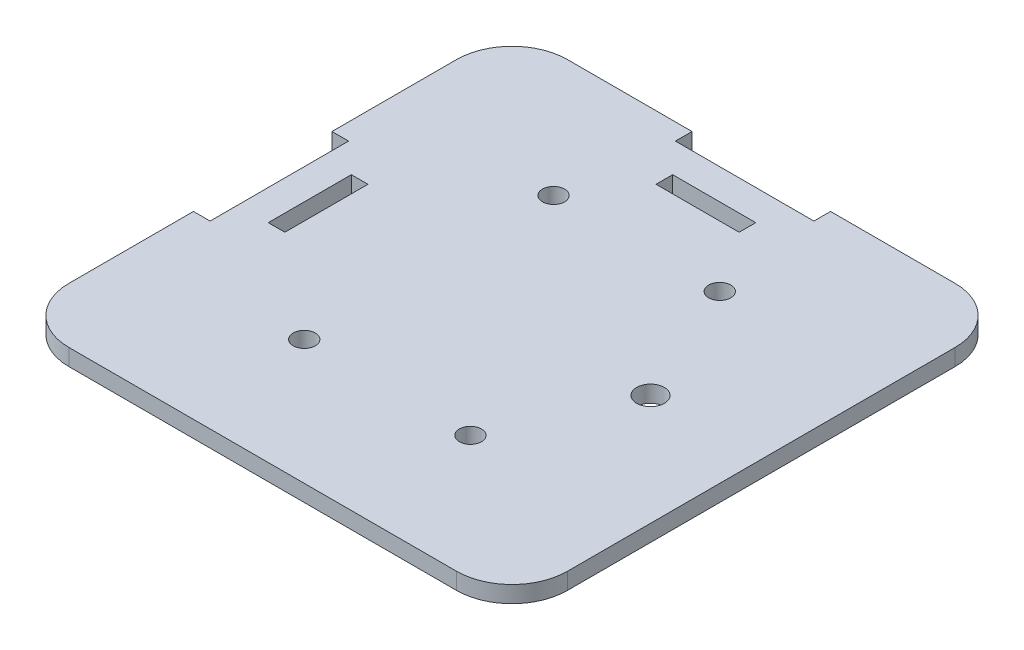
SolidWorks part; units mm, degrees
ref_plane "Front Plane" through (0, 0, 0) normal (0, 0, 1) x (1, 0, 0)
ref_plane "Top Plane" through (0, 0, 0) normal (0, 1, 0) x (1, 0, 0)
ref_plane "Right Plane" through (0, 0, 0) normal (1, 0, 0) x (0, 0, -1)
sketch "Sketch1" plane through (0, 0, 0) normal (0, 1, 0) x (1, 0, 0)
  line L1 (35, -45) -> (-35, -45)
  line L2 (45, -35) -> (45, 35)
  line L3 (35, 45) -> (-35, 45)
  line L4 (-45, -35) -> (-45, 35)
  line L5 (45, -45) -> (-45, 45) construction
  line L6 (45, 45) -> (-45, -45) construction
  line L7 (-45, 12.5) -> (-42, 12.5)
  line L8 (-45, 12.5) -> (-45, -12.5)
  line L9 (-45, -12.5) -> (-42, -12.5)
  line L10 (-42, 12.5) -> (-42, -12.5)
  line L11 (-12.5, 45) -> (12.5, 45)
  line L12 (-12.5, 45) -> (-12.5, 42)
  line L13 (-12.5, 42) -> (12.5, 42)
  line L14 (12.5, 45) -> (12.5, 42)
  arc A0 (-45, -35) -> (-35, -45) centre (-35, -35) ccw
  arc A1 (35, -45) -> (45, -35) centre (35, -35) ccw
  arc A2 (45, 35) -> (35, 45) centre (35, 35) ccw
  arc A3 (-45, 35) -> (-35, 45) centre (-35, 35) cw
  point P0 (0, 0)
  point P22 (-42, 0)
  point P23 (-45, 0)
  point P28 (0, 42)
  point P29 (0, 45)
  dimension "D1" = 10
  dimension "D2" = 3
  dimension "D3" = 25
  dimension "D4" = 0
  dimension "D5" = 3
  dimension "D6" = 25
  dimension "D7" = 0
  dimension "D8" = 90
  dimension "D9" = 90
extrude "Boss-Extrude1" add sketch "Sketch1" along normal blind 3 contours A3 L4 L7 L10 L9 A0 L1 A1 L2 A2 L3 L14 L13 L12 region at (0.4149, 0, 0.4149)
sketch "Sketch2" plane through (0, 3, 0) normal (0, 1, 0) x (1, 0, 0)
  line L0 (0, -1.65) -> (0, 1.65) construction
  line L1 (-1.65, 0) -> (1.65, 0) construction
  circle A0 centre (-15, 22.5) radius 2
  circle A1 centre (15, 22.5) radius 2
  circle A2 centre (15, -22.5) radius 2
  circle A3 centre (-15, -22.5) radius 2
  dimension "D1" = 15
  dimension "D2" = 22.5
extrude "Cut-Extrude1" cut sketch "Sketch2" against normal blind 3
sketch "Sketch3" plane through (0, 3, 0) normal (0, 1, 0) x (1, 0, 0)
  line L1 (7.5, 33.5) -> (-7.5, 33.5)
  line L2 (7.5, 33.5) -> (7.5, 36.5)
  line L3 (7.5, 36.5) -> (-7.5, 36.5)
  line L4 (-7.5, 33.5) -> (-7.5, 36.5)
  line L5 (7.5, 33.5) -> (-7.5, 36.5) construction
  line L6 (7.5, 36.5) -> (-7.5, 33.5) construction
  line L7 (-33.5, -7.5) -> (-36.5, -7.5)
  line L8 (-33.5, -7.5) -> (-33.5, 7.5)
  line L9 (-33.5, 7.5) -> (-36.5, 7.5)
  line L10 (-36.5, -7.5) -> (-36.5, 7.5)
  line L11 (-33.5, -7.5) -> (-36.5, 7.5) construction
  line L12 (-33.5, 7.5) -> (-36.5, -7.5) construction
  point P0 (0, 35)
  point P5 (-35, 0)
  dimension "D1" = 15
  dimension "D2" = 3
  dimension "D3" = 35
  dimension "D4" = 0
  dimension "D5" = 3
  dimension "D6" = 15
  dimension "D7" = 0
  dimension "D8" = 35
extrude "Cut-Extrude2" cut sketch "Sketch3" against normal blind 10
sketch "Sketch4" plane through (0, 3, 0) normal (0, 1, 0) x (1, 0, 0)
  circle A0 centre (25, 0) radius 2.5
  dimension "D1" = 25
extrude "Cut-Extrude3" cut sketch "Sketch4" against normal blind 14
